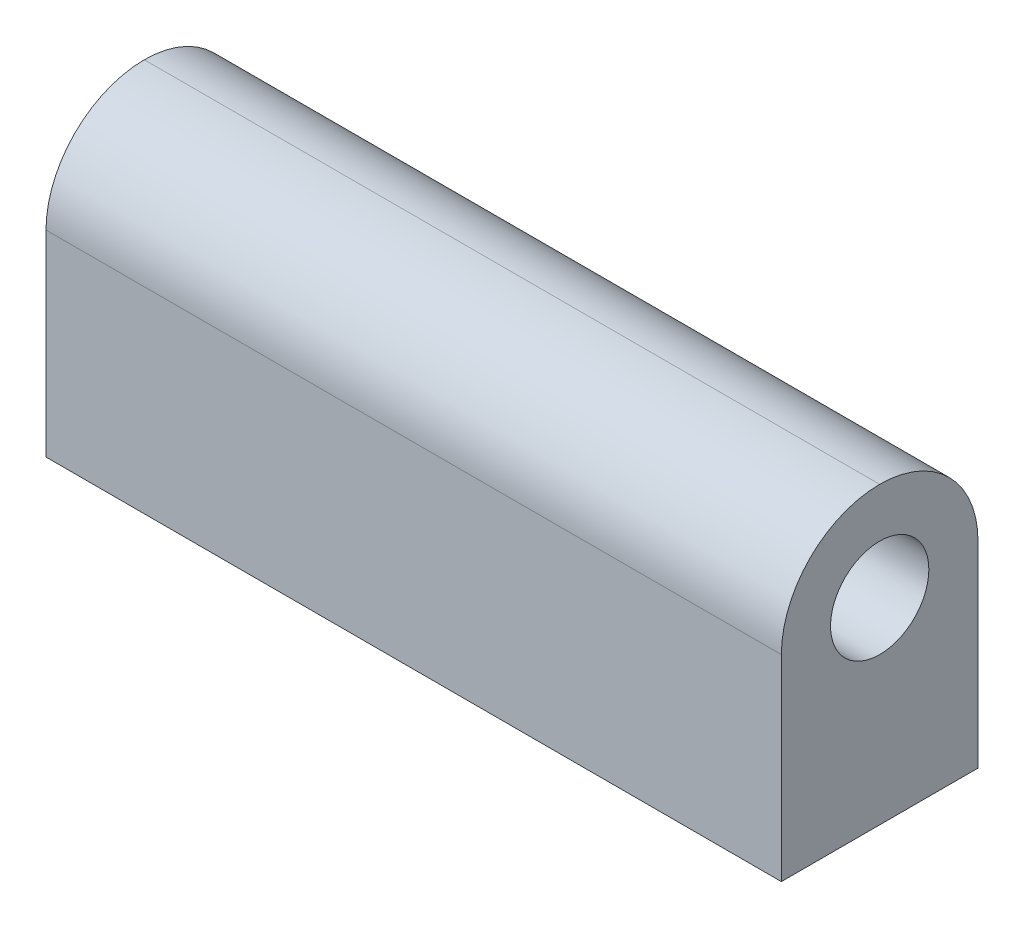
SolidWorks part; units mm, degrees
ref_plane "Front Plane" through (0, 0, 0) normal (0, 0, 1) x (1, 0, 0)
ref_plane "Top Plane" through (0, 0, 0) normal (0, 1, 0) x (1, 0, 0)
ref_plane "Right Plane" through (0, 0, 0) normal (1, 0, 0) x (0, 0, -1)
sketch "Sketch1" plane through (0, 0, 0) normal (0, 1, 0) x (1, 0, 0)
  line L1 (-18.7, -5) -> (18.7, -5)
  line L2 (-18.7, -5) -> (-18.7, 5)
  line L3 (-18.7, 5) -> (18.7, 5)
  line L4 (18.7, -5) -> (18.7, 5)
  line L5 (-18.7, -5) -> (18.7, 5) construction
  line L6 (-18.7, 5) -> (18.7, -5) construction
  point P0 (0, 0)
  dimension "D1" = 37.4
  dimension "D2" = 10
extrude "Boss-Extrude1" add sketch "Sketch1" along normal blind 15
fillet "Fillet1" radius 5 2 edges at (0, 15, -5) (0, 15, 5)
hole_wizard "CBORE for M5 Hex Head Bolt2" positions "Sketch9" profile "Sketch11" counterbore size "M5" standard "ANSI Metric"
sketch "Sketch9" plane through (-18.7, 0, 0) normal (-1, 0, 0) x (0, 0, 1)
  point P0 (0, 10)
  point P5 (0, 5)
  point P6 (0, 5)
sketch "Sketch11" plane through (-18.7, 10, 0) normal (0, 1, 0) x (0, 0, 1)
  line L0 (0, 0) -> (0, 11.3519)
  line L1 (0, 11.3519) -> (2.25, 10)
  line L2 (2.25, 10) -> (2.25, 8)
  line L3 (2.25, 8) -> (2.5, 8)
  line L4 (2.5, 8) -> (2.5, 0)
  line L5 (2.5, 0) -> (0, 0)
  line L10 (0, 11.3519) -> (-2.25, 10) construction
  line L11 (0, -6.35) -> (0, 107.95) construction
  dimension "Hole Dia." = 4.5
  dimension "Hole Depth" = 10
  dimension "C'Bore Dia." = 5
  dimension "C'Bore Depth" = 8
  dimension "Drill Angle" = 118
mirror "Mirror1" about plane through (0, 0, 0) normal (1, 0, 0) of "CBORE for M5 Hex Head Bolt2"
hole_wizard "Ø1.0mm Dowel Hole1" positions "Sketch12" profile "Sketch14" hole size "Ø1.0" standard "ANSI Metric"
sketch "Sketch12" plane through (0, 0, 0) normal (0, -1, 0) x (-1, 0, 0)
  line L0 (-5, 0) -> (5, 0)
  point P1 (-5, 0)
  point P2 (5, 0)
  point P9 (0, 0)
  dimension "D1" = 10
sketch "Sketch14" plane through (5, 0, 0) normal (1, 0, 0) x (0, 0, -1)
  line L0 (0, 0) -> (0, 5.7022)
  line L1 (0, 5.7022) -> (2.5, 4.2)
  line L2 (2.5, 4.2) -> (2.5, 0)
  line L5 (2.5, 0) -> (0, 0)
  line L10 (0, 5.7022) -> (-2.5, 4.2) construction
  line L11 (0, -6.35) -> (0, 107.95) construction
  dimension "Hole Dia." = 5
  dimension "Hole Depth" = 4.2
  dimension "Drill Angle" = 118
